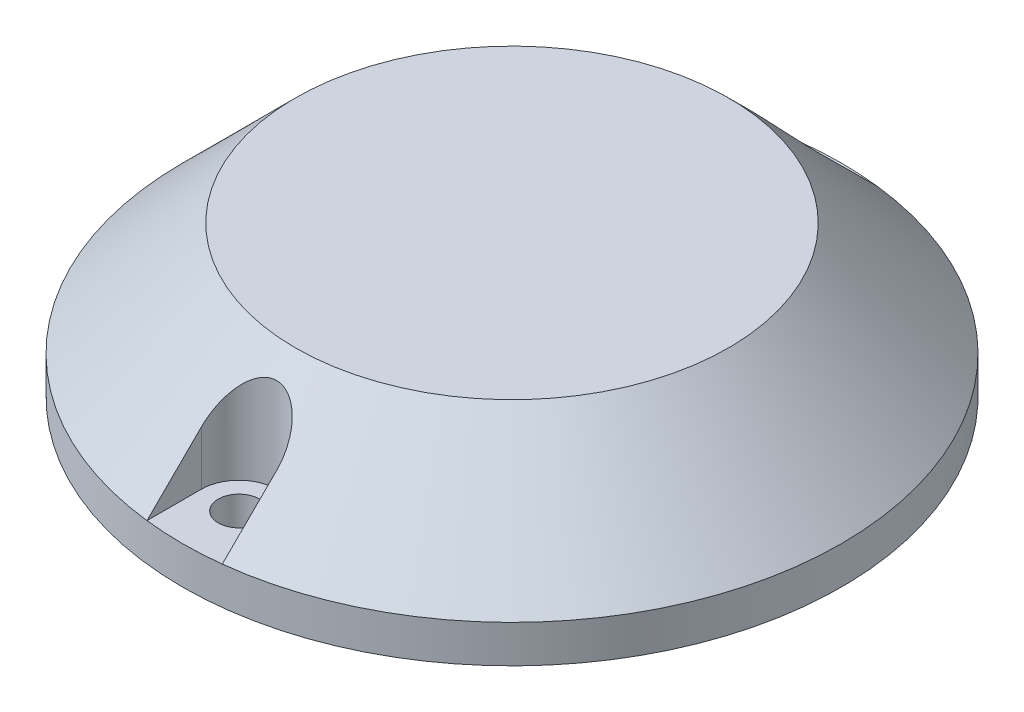
SolidWorks part; units mm, degrees
ref_plane "Front Plane" through (0, 0, 0) normal (0, 0, 1) x (1, 0, 0)
ref_plane "Top Plane" through (0, 0, 0) normal (0, 1, 0) x (1, 0, 0)
ref_plane "Right Plane" through (0, 0, 0) normal (1, 0, 0) x (0, 0, -1)
sketch "Sketch1" plane through (0, 0, 0) normal (0, 1, 0) x (1, 0, 0)
  line L2 (-2, 14.5) -> (-2, 17.3853)
  line L4 (2, 14.5) -> (2, 17.3853)
  line L6 (-2, -14.5) -> (-2, -17.3853)
  line L8 (2, -14.5) -> (2, -17.3853)
  circle A0 centre (0, 0) radius 14.5 construction
  arc A1 (-2, 17.3853) -> (-2, -17.3853) centre (0, 0) ccw
  arc A2 (-2, 14.5) -> (2, 14.5) centre (0, 14.5) ccw
  arc A3 (2, -14.5) -> (-2, -14.5) centre (0, -14.5) ccw
  arc A4 (2, -17.3853) -> (2, 17.3853) centre (0, 0) ccw
  dimension "D1" = 29
  dimension "D2" = 4
  dimension "D3" = 4
  dimension "D4" = 35
extrude "Boss-Extrude1" add sketch "Sketch1" along normal blind 2
sketch "Sketch2" plane through (0, 2, 0) normal (0, 1, 0) x (1, 0, 0)
  circle A0 centre (0, 0) radius 11.5
  dimension "D1" = 23
extrude "Boss-Extrude2" add sketch "Sketch2" along normal blind 6
chamfer "Chamfer1" distance 6 angle 45 1 edges at (0, 2, 11.5)
sketch "Sketch6" plane through (0, 0, 0) normal (0, -1, 0) x (1, 0, 0)
  circle A0 centre (0, 14.5) radius 1.1
  circle A1 centre (0, -14.5) radius 1.1
  circle A5 centre (0, 0) radius 17.5
  dimension "D1" = 2.2
  dimension "D2" = 2.2
extrude "Boss-Extrude3" add sketch "Sketch6" against normal blind 2
sketch "Sketch7" plane through (0, 0, 0) normal (0, -1, 0) x (1, 0, 0)
  circle A0 centre (0, 0) radius 11.5
  dimension "D1" = 23
extrude "Cut-Extrude1" cut sketch "Sketch7" against normal blind 7
sketch "Sketch8" plane through (0, 7, 0) normal (0, -1, 0) x (1, 0, 0)
  circle A0 centre (0, 0) radius 10 construction
  dimension "D1" = 20
chamfer "Chamfer2" distance 1.5 angle 45 1 edges at (0, 7, -11.5)
chamfer "Chamfer3" distance 1 angle 45 1 edges at (0, 0, -11.5)
